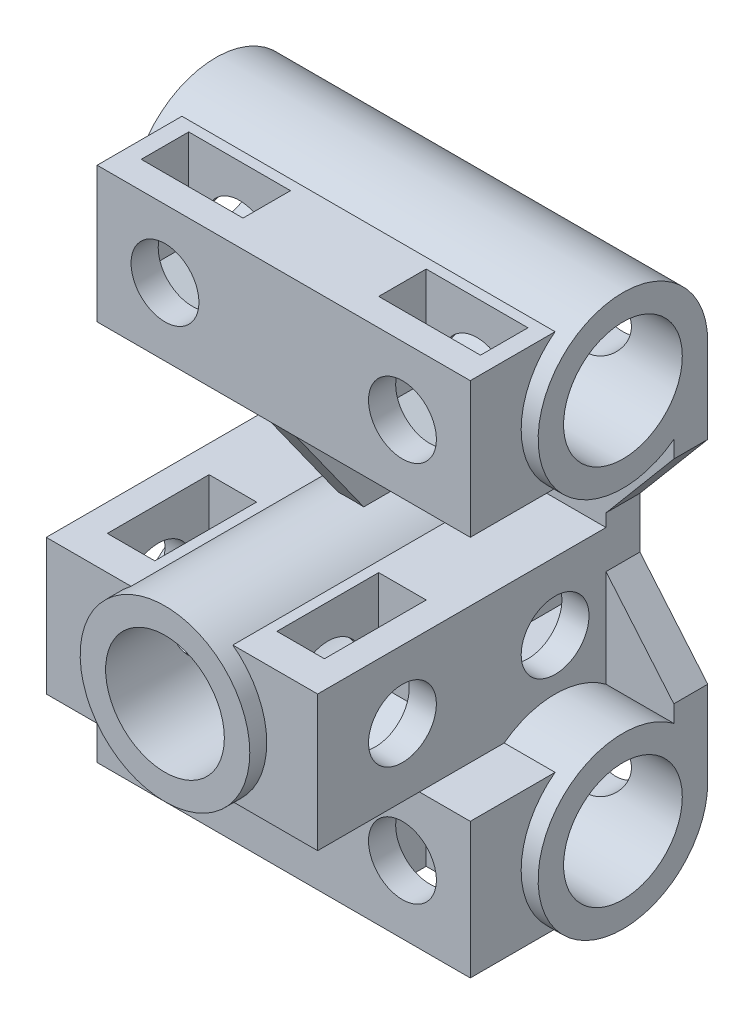
SolidWorks part; units mm, degrees
ref_plane "Front Plane" through (0, 0, 0) normal (0, 0, 1) x (1, 0, 0)
ref_plane "Top Plane" through (0, 0, 0) normal (0, 1, 0) x (1, 0, 0)
ref_plane "Right Plane" through (0, 0, 0) normal (1, 0, 0) x (0, 0, -1)
sketch "Sketch1" plane through (0, 0, 0) normal (0, 0, 1) x (1, 0, 0)
  circle A0 centre (0, 0) radius 5
  circle A1 centre (0, 0) radius 3.5
  dimension "D1" = 7
  dimension "D2" = 10
extrude "Boss-Extrude1" add sketch "Sketch1" along normal blind 20
ref_axis "Smooth Rod Axis" through (0, 0, 20) along (0, 0, -1)
sketch "Sketch4" plane through (0, 0, 0) normal (1, 0, 0) x (0, 0, -1)
  line L0 (-20, 0) -> (0, 0) construction
  line L2 (0, 5.5) -> (0, -5.5) construction
  circle A1 centre (-5, 14.5) radius 5
  circle A3 centre (-5, -8) radius 5
  dimension "D1" = 22.5
  dimension "D2" = 10
  dimension "D3" = 8
extrude "Boss-Extrude3" add sketch "Sketch4" along normal blind 12 and the other way blind 12
ref_axis "Upper Crossbeam Axis" through (-12, 14.5, 5) along (1, 0, 0)
ref_axis "Lower Crossbeam Axis" through (-12, -8, 5) along (1, 0, 0)
ref_plane "Threaded Rod Plane" through (0, 0, 5) normal (0, 0, -1) x (-1, 0, 0)
sketch "Sketch6" plane through (0, 0, 5) normal (0, 0, -1) x (-1, 0, 0)
  line L0 (3, 4) -> (8, 4)
  line L1 (8, 4) -> (8, -4)
  line L2 (8, -4) -> (3, -4)
  line L3 (-3, 4) -> (-8, 4)
  line L4 (-8, 4) -> (-8, -4)
  line L5 (-8, -4) -> (-3, -4)
  line L6 (13.2374, 0) -> (-9.8143, 0) construction
  line L7 (0, 7.2503) -> (0, -6.5178) construction
  arc A0 (3, 4) -> (3, -4) centre (0, 0) cw
  circle A2 centre (0, 0) radius 5 construction
  arc A3 (-3, 4) -> (-3, -4) centre (0, 0) ccw
  dimension "D1" = 8
  dimension "D2" = 8
extrude "Boss-Extrude4" add sketch "Sketch6" against normal offset from surface 1 and the other way offset from surface 1 up to face at (5, 0, 20) other way up to face at (5, 0, 0)
sketch "Sketch9" plane through (0, 0, 0) normal (0, 0, 1) x (1, 0, 0)
  line L0 (12, 14.5) -> (-12, 14.5)
  line L1 (12, -8) -> (-12, -8)
  line L2 (0, 21.6749) -> (0, -11.1648) construction
  line L3 (12, -8) -> (12, -3)
  line L4 (-8, 1.75) -> (-8, 4.75)
  line L5 (-12, -8) -> (-12, -3)
  line L6 (-12, -3) -> (-8, 1.75)
  line L8 (-8, 4.75) -> (-12, 9.5)
  line L9 (-12, 9.5) -> (-12, 14.5)
  line L10 (-12, 19.5) -> (-12, 9.5) construction
  line L11 (-8, 4) -> (-8, -4) construction
  line L20 (12, -3) -> (8, 1.75)
  line L21 (8, 1.75) -> (8, 4.75)
  line L22 (12, 14.5) -> (12, 9.5)
  line L39 (8, 4.75) -> (12, 9.5)
  line L40 (8, 3.25) -> (-7.6049, 3.25) construction
  line L42 (-12, -3) -> (-12, -13) construction
  line L49 (-12, 14.5) -> (12, 14.5) construction
  line L50 (-12, -8) -> (12, -8) construction
  circle A2 centre (0, 0) radius 3.5
  circle A3 centre (0, 0) radius 3.5 construction
  dimension "D1" = 3
extrude "Boss-Extrude6" add sketch "Sketch9" along normal blind 2
sketch "Sketch11" plane through (0, 0, 0) normal (1, 0, 0) x (0, 0, -1)
  line L0 (-11.7826, 14.5) -> (6.4042, 14.5) construction
  line L1 (-5, 21.9) -> (-5, -18.7092) construction
  line L2 (-9.6558, -8) -> (15.2974, -8) construction
  line L3 (-8, 18.5) -> (-13, 18.5)
  line L4 (-13, 18.5) -> (-13, 10.5)
  line L5 (-13, 10.5) -> (-8, 10.5)
  line L12 (-8, -12) -> (-13, -12)
  line L13 (-13, -12) -> (-13, -4)
  line L14 (-13, -4) -> (-8, -4)
  arc A0 (-8, 18.5) -> (-8, 10.5) centre (-5, 14.5) ccw
  arc A1 (-8, -4) -> (-8, -12) centre (-5, -8) ccw
  circle A4 centre (-5, 14.5) radius 5 construction
  circle A5 centre (-5, -8) radius 5 construction
  dimension "D1" = 8
  dimension "D2" = 8
  dimension "D3" = 8
  dimension "D4" = 8
extrude "Boss-Extrude7" add sketch "Sketch11" along normal offset from surface 1 and the other way offset from surface 1 up to face at (12, 14.5, 0) other way up to face at (-12, 14.5, 0)
sketch "Sketch13" plane through (0, 0, 0) normal (0, 0, 1) x (1, 0, 0)
  line L0 (-12, 14.5) -> (12, 14.5) construction
  line L1 (-12, -8) -> (12, -8) construction
  line L2 (-11, 18.5) -> (-11, 10.5) construction
  line L3 (11, 18.5) -> (11, 10.5) construction
  line L4 (11, -4) -> (11, -12) construction
  line L5 (-11, -4) -> (-11, -12) construction
  circle A0 centre (7, 14.5) radius 2
  circle A1 centre (-7, 14.5) radius 2
  circle A2 centre (7, -8) radius 2
  circle A3 centre (-7, -8) radius 2
  dimension "D1" = 4
  dimension "D2" = 4
  dimension "D3" = 4
  dimension "D4" = 4
  dimension "D5" = 4
extrude "Cut-Extrude3" cut sketch "Sketch13" along normal up to surface (13 mm away) up to face at (0, 14.5, 13)
ref_plane "Front Nut Plane" through (0, 0, 10) normal (0, 0, -1) x (-1, 0, 0)
sketch "Sketch14" plane through (0, 0, 10) normal (0, 0, -1) x (-1, 0, 0)
  line L0 (4, 16.2321) -> (4, 19.5)
  line L1 (7, 17.9641) -> (4, 16.2321) construction
  line L2 (4, 16.2321) -> (4, 12.7679)
  line L3 (4, 12.7679) -> (7, 11.0359)
  line L4 (7, 11.0359) -> (10, 12.7679)
  line L5 (10, 12.7679) -> (10, 16.2321)
  line L6 (10, 16.2321) -> (7, 17.9641) construction
  line L7 (-7, 17.9641) -> (-10, 16.2321) construction
  line L8 (-10, 16.2321) -> (-10, 12.7679)
  line L9 (-10, 12.7679) -> (-7, 11.0359)
  line L10 (-7, 11.0359) -> (-4, 12.7679)
  line L11 (-4, 12.7679) -> (-4, 16.2321)
  line L12 (-4, 16.2321) -> (-7, 17.9641) construction
  line L13 (-7, -4.5359) -> (-10, -6.2679)
  line L14 (-10, -6.2679) -> (-10, -9.7321)
  line L15 (-10, -9.7321) -> (-7, -11.4641) construction
  line L16 (-7, -11.4641) -> (-4, -9.7321) construction
  line L17 (-4, -9.7321) -> (-4, -6.2679)
  line L18 (-4, -6.2679) -> (-7, -4.5359)
  line L19 (7, -4.5359) -> (4, -6.2679)
  line L20 (4, -6.2679) -> (4, -9.7321)
  line L21 (4, -9.7321) -> (7, -11.4641) construction
  line L22 (7, -11.4641) -> (10, -9.7321) construction
  line L23 (10, -9.7321) -> (10, -6.2679)
  line L24 (10, -6.2679) -> (7, -4.5359)
  line L25 (4, 19.5) -> (10, 19.5)
  line L26 (10, 19.5) -> (10, 16.2321)
  line L27 (-10, 16.2321) -> (-10, 19.5)
  line L28 (-10, 19.5) -> (-4, 19.5)
  line L29 (-4, 19.5) -> (-4, 16.2321)
  line L30 (10, -9.7321) -> (10, -13)
  line L31 (10, -13) -> (4, -13)
  line L32 (4, -13) -> (4, -9.7321)
  line L33 (-10, -9.7321) -> (-10, -13)
  line L34 (-10, -13) -> (-4, -13)
  line L35 (-4, -13) -> (-4, -9.7321)
  line L36 (-12, -13) -> (12, -13) construction
  line L38 (12, 19.5) -> (-12, 19.5) construction
  circle A0 centre (7, 14.5) radius 3 construction
  circle A1 centre (-7, 14.5) radius 3 construction
  circle A2 centre (-7, -8) radius 3 construction
  circle A3 centre (7, -8) radius 3 construction
  dimension "D1" = 6
extrude "Cut-Extrude4" cut sketch "Sketch14" against normal mid plane 2.8
sketch "Sketch15" plane through (0, 0, 0) normal (1, 0, 0) x (0, 0, -1)
  line L1 (-20, 0) -> (0, 0) construction
  line L5 (-19, 4) -> (-19, -4) construction
  line L7 (0, 4.75) -> (0, 1.75) construction
  circle A0 centre (-5, 0) radius 2
  circle A1 centre (-14, 0) radius 2
  dimension "D1" = 4
  dimension "D2" = 5
  dimension "D3" = 5
extrude "Cut-Extrude5" cut sketch "Sketch15" along normal through all and the other way through all
ref_plane "Right Nut Plane" through (-5, 0, 0) normal (1, 0, 0) x (0, 0, -1)
sketch "Sketch16" plane through (-5, 0, 0) normal (1, 0, 0) x (0, 0, -1)
  line L0 (-17, 1.7321) -> (-17, 5)
  line L1 (-14, 3.4641) -> (-17, 1.7321) construction
  line L2 (-17, 1.7321) -> (-17, -1.7321)
  line L3 (-17, -1.7321) -> (-14, -3.4641)
  line L4 (-14, -3.4641) -> (-11, -1.7321)
  line L5 (-11, -1.7321) -> (-11, 1.7321)
  line L6 (-11, 1.7321) -> (-14, 3.4641) construction
  line L7 (-1.5359, 0) -> (-3.2679, 3) construction
  line L8 (-3.2679, 3) -> (-6.7321, 3)
  line L9 (-6.7321, 3) -> (-8.4641, 0)
  line L10 (-8.4641, 0) -> (-6.7321, -3)
  line L11 (-6.7321, -3) -> (-3.2679, -3)
  line L12 (-3.2679, -3) -> (-1.5359, 0) construction
  line L13 (-17, 5) -> (-11, 5)
  line L14 (-11, 5) -> (-11, 1.7321)
  line L15 (-3.2679, 3) -> (0, 3)
  line L16 (0, 3) -> (0, -3)
  line L17 (0, -3) -> (-3.2679, -3)
  line L18 (0, 4.75) -> (0, 1.75) construction
  line L19 (-2, 5) -> (-20, 5) construction
  circle A0 centre (-14, 0) radius 3 construction
  circle A1 centre (-5, 0) radius 3 construction
  circle A2 centre (-5, 0) radius 2 construction
  dimension "D1" = 6
extrude "Cut-Extrude6" cut sketch "Sketch16" against normal mid plane 2.8
ref_plane "Left Nut Plane" through (5, 0, 0) normal (1, 0, 0) x (0, 0, -1)
sketch "Sketch22" plane through (5, 0, 0) normal (1, 0, 0) x (0, 0, -1)
  line L0 (-17, 1.7321) -> (-17, 5)
  line L1 (-14, 3.4641) -> (-17, 1.7321) construction
  line L2 (-17, 1.7321) -> (-17, -1.7321)
  line L3 (-17, -1.7321) -> (-14, -3.4641)
  line L4 (-14, -3.4641) -> (-11, -1.7321)
  line L5 (-11, -1.7321) -> (-11, 1.7321)
  line L6 (-11, 1.7321) -> (-14, 3.4641) construction
  line L7 (-1.5359, 0) -> (-3.2679, 3) construction
  line L8 (-3.2679, 3) -> (-6.7321, 3)
  line L9 (-6.7321, 3) -> (-8.4641, 0)
  line L10 (-8.4641, 0) -> (-6.7321, -3)
  line L11 (-6.7321, -3) -> (-3.2679, -3)
  line L12 (-3.2679, -3) -> (-1.5359, 0) construction
  line L13 (-17, 5) -> (-11, 5)
  line L14 (-11, 5) -> (-11, 1.7321)
  line L15 (-3.2679, 3) -> (0, 3)
  line L16 (0, 3) -> (0, -3)
  line L17 (0, -3) -> (-3.2679, -3)
  line L20 (-2, 5) -> (-20, 5) construction
  line L21 (0, 1.75) -> (0, 4.75) construction
  circle A0 centre (-14, 0) radius 3 construction
  circle A1 centre (-5, 0) radius 3 construction
  circle A4 centre (-5, 0) radius 2 construction
  circle A5 centre (-14, 0) radius 2 construction
  dimension "D1" = 6
extrude "Cut-Extrude11" cut sketch "Sketch22" against normal mid plane 2.8
sketch "Sketch23" plane through (0, 0, 0) normal (1, 0, 0) x (0, 0, -1)
  line L0 (-8, 10.5) -> (-13, 10.5)
  line L1 (-13, 10.5) -> (-8, 3.5)
  line L2 (-8, 3.5) -> (-2, 3.5)
  line L3 (-2, 3.5) -> (-2, 10.5)
  line L4 (-2, 4.75) -> (-2, 9.5) construction
  line L5 (0, 3.5) -> (-20, 3.5) construction
  arc A0 (-8, 10.5) -> (-2, 10.5) centre (-5, 14.5) ccw
  arc A1 (0, 14.5) -> (-2, 10.5) centre (-5, 14.5) ccw construction
  dimension "D1" = 6
extrude "Boss-Extrude8" add sketch "Sketch23" along normal mid plane 1.5
sketch "Sketch20" plane through (0, 0, 0) normal (0, 0, 1) x (1, 0, 0)
  circle A0 centre (0, 0) radius 3.5
  circle A1 centre (0, 0) radius 3.5 construction
extrude "Cut-Extrude9" cut sketch "Sketch20" along normal through all
sketch "Sketch21" plane through (12, 0, 0) normal (1, 0, 0) x (0, 0, -1)
  circle A0 centre (-5, 14.5) radius 3.5
  circle A1 centre (-5, -8) radius 3.5
  dimension "D1" = 7
extrude "Cut-Extrude10" cut sketch "Sketch21" against normal up to surface (24 mm away) up to face at (-12, 12.059, 3.118)
split "Split1" [suppressed] bodies to split 125
